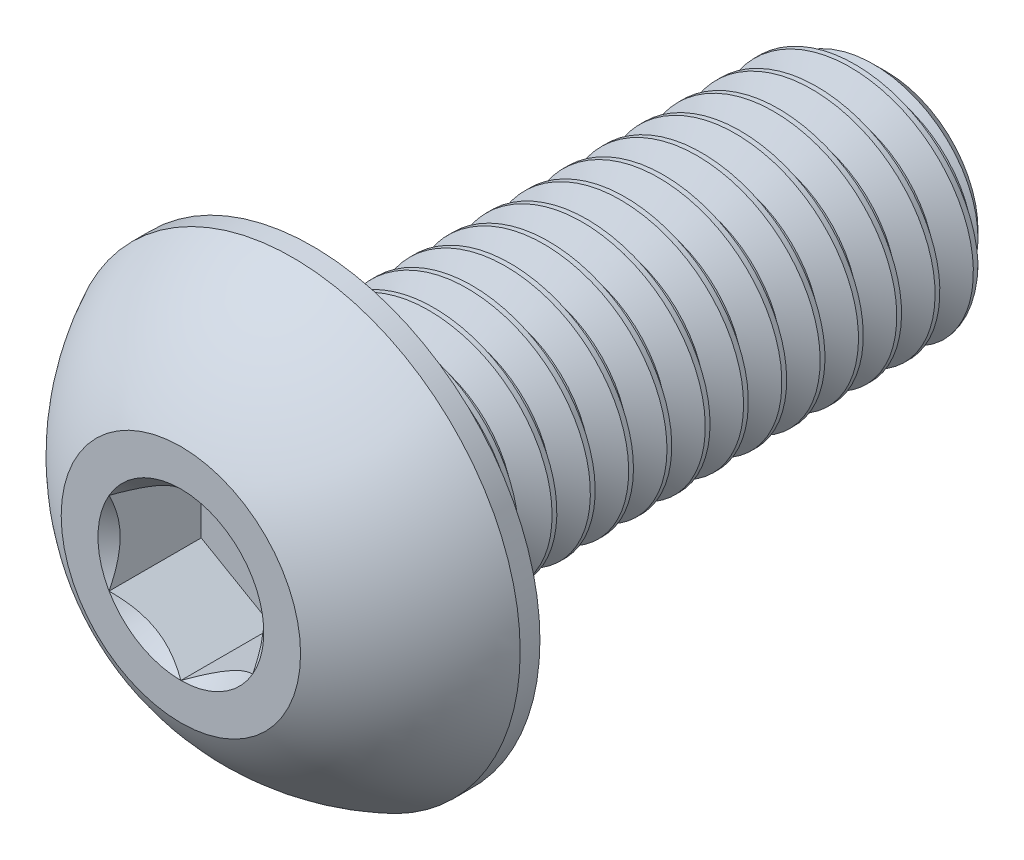
SolidWorks part; units mm, degrees
ref_plane "Front" through (0, 0, 0) normal (0, 0, 1) x (1, 0, 0)
ref_plane "Top" through (0, 0, 0) normal (0, 1, 0) x (1, 0, 0)
ref_plane "Right" through (0, 0, 0) normal (1, 0, 0) x (0, 0, -1)
sketch "Sketch1" plane through (0, 0, 0) normal (1, 0, 0) x (0, 0, -1)
  line L2 (2.75, 2.5) -> (14.75, 2.5)
  line L3 (14.75, 2.5) -> (14.75, 0)
  line L4 (14.75, 0) -> (2.75, 0)
  line L6 (2.3375, 4.75) -> (2.75, 4.75) construction
  line L7 (14.75, 2.5) -> (14.75, -2.5) construction
  line L8 (0, 0) -> (2.75, 0) construction
  line L9 (2.75, 4.75) -> (2.75, -4.75) construction
  line L11 (2.75, 2.5) -> (2.75, 0)
  line L13 (0, 1.5) -> (0, -1.5) construction
  line L14 (0, 1.5) -> (0, 2.5) construction
  arc A3 (0, 2.5) -> (2.3375, 4.75) centre (4.6581, 0) cw construction
  dimension "D1" = 0.4125
  dimension "Head Ht" = 2.75
  dimension "Head Dia" = 9.5
  dimension "Dia" = 5
  dimension "Lg" = 12
  dimension "Hex" = 3
revolve "Revolve1" add sketch "Sketch1" angle 360 mid plane about L4
sketch "Sketch3" plane through (0, 0, -14.75) normal (0, 0, -1) x (-1, 0, 0)
  circle A0 centre (0, 0) radius 2.5
curve "Helix/Spiral1" pitch 0.8 height 12.8 radius 2.5 centre (0, 0, -14.75) axis (0, 0, 1) start towards (0, 1, 0)
sketch "Sketch2" plane through (0, 0, 0) normal (1, 0, 0) x (0, 0, -1)
  line L0 (14.75, 2.5) -> (15.45, 2.5)
  line L1 (15.45, 2.5) -> (15.15, 1.9804)
  line L2 (15.15, 1.9804) -> (15.05, 1.9804)
  line L3 (15.05, 1.9804) -> (14.75, 2.5)
  line L4 (14.9, 2.2402) -> (15.3, 2.2402) construction
  dimension "D1" = 60
  dimension "D2" = 0.1
  dimension "D3" = 0.4
chamfer "Chamfer1" distance 0.6 angle 45 1 edges at (0, 2.5, -14.75)
sweep "Cut-Sweep1" cut profiles "Sketch2" path "Helix/Spiral1"
sketch "Sketch7" plane through (0, 0, 0) normal (1, 0, 0) x (0, 0, -1)
  line L6 (2.3375, 4.75) -> (2.75, 4.75) construction
  line L8 (0, 0) -> (2.75, 0) construction
  line L11 (2.75, 4.75) -> (2.75, -4.75) construction
  line L12 (2.3375, 4.75) -> (2.75, 4.75)
  line L13 (0, 0) -> (2.75, 0)
  line L14 (0, 1.5) -> (0, -1.5) construction
  line L15 (2.75, 4.75) -> (2.75, 0)
  line L16 (0, 2.5) -> (0, 0)
  arc A2 (2.3375, 4.75) -> (0, 2.5) centre (4.6581, 0) ccw construction
  arc A3 (2.3375, 4.75) -> (0, 2.5) centre (4.6581, 0) ccw
revolve "Revolve2" add sketch "Sketch7" angle 360 mid plane about L13
sketch "Sketch5" plane through (0, 0, 0) normal (0, 0, 1) x (1, 0, 0)
  line L1 (1.5, -0.866) -> (1.5, 0.866)
  line L2 (1.5, 0.866) -> (0, 1.7321)
  line L3 (0, 1.7321) -> (-1.5, 0.866)
  line L4 (-1.5, 0.866) -> (-1.5, -0.866)
  line L5 (-1.5, -0.866) -> (0, -1.7321)
  line L6 (0, -1.7321) -> (1.5, -0.866)
  circle A0 centre (0, 0) radius 1.5 construction
extrude "Cut-Extrude2" cut sketch "Sketch5" against normal blind 1.925
sketch "Sketch6" plane through (0, 0, 0) normal (0, 0, 1) x (1, 0, 0)
  circle A0 centre (0, 0) radius 1.7321
extrude "Cut-Extrude3" cut sketch "Sketch6" against normal blind 1.925 draft 45
sketch "Sketch9" [suppressed] plane through (0, 0, -6.6) normal (0, 0, 1) x (1, 0, 0)
  circle A2 centre (0, 0) radius 6
extrude "Boss-Extrude2" [suppressed] add sketch "Sketch9" against normal offset from surface (19 mm away) 32
sketch "Sketch10" plane through (0, 0, 0) normal (1, 0, 0) x (0, 0, -1)
  line L0 (14.75, 2.5) -> (14.75, -2.5) construction
  point P0 (13.55, -2.5)
  dimension "D1" = 1.2
equation "\"D3@Helix/Spiral1\" = \"Lg@Sketch1\" + \"D4@Helix/Spiral1\""
equation "\"D2@Sketch2\" = \"D4@Helix/Spiral1\" * .125"
equation "\"D3@Sketch2\" = \"D4@Helix/Spiral1\" * .5"
equation "\"D1@Chamfer1\" = \"D4@Helix/Spiral1\" * .75"
equation "\"D1@Cut-Extrude2\" = \"Head Ht@Sketch1\" * .7"
equation "\"D1@Sketch1\" = \"Head Ht@Sketch1\" * .15"
equation "\"D1@Sketch10\" = \"D4@Helix/Spiral1\" * 1.5"
equation "\"D1@Cut-Extrude3\" = \"D1@Cut-Extrude2\""
